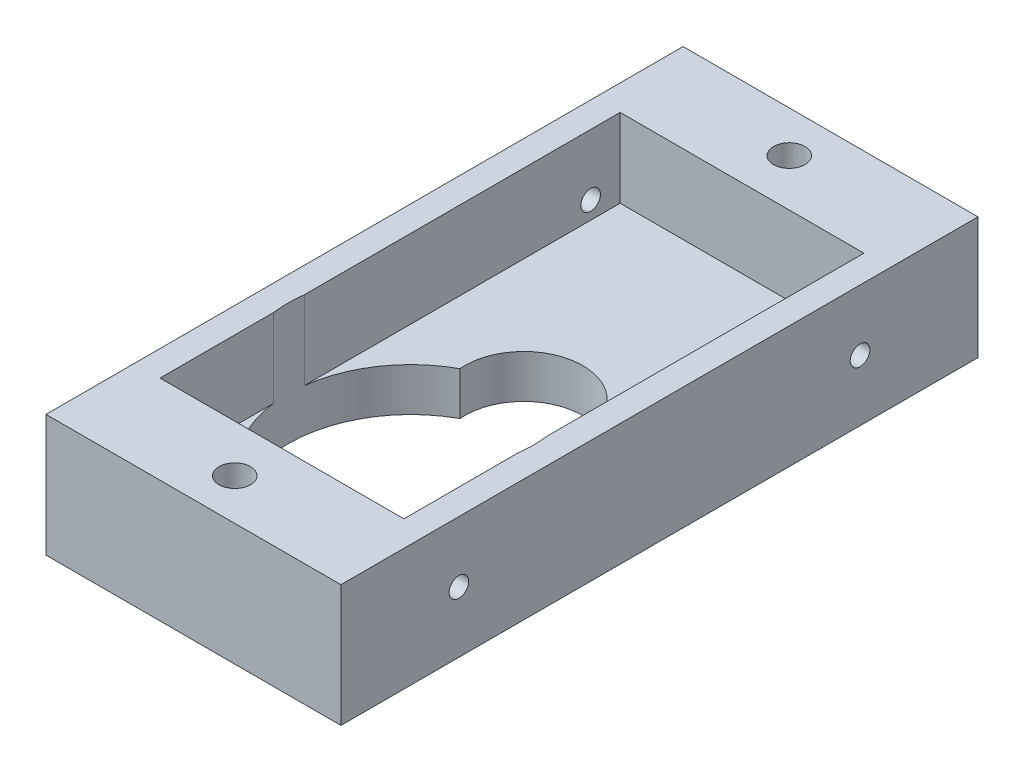
SolidWorks part; units mm, degrees
ref_plane "前视基准面" through (0, 0, 0) normal (0, 0, 1) x (1, 0, 0)
ref_plane "上视基准面" through (0, 0, 0) normal (0, 1, 0) x (1, 0, 0)
ref_plane "右视基准面" through (0, 0, 0) normal (1, 0, 0) x (0, 0, -1)
other "Configuration Table"
sketch "草图1" plane through (0, 0, 0) normal (0, 1, 0) x (1, 0, 0)
  line L1 (0, 0) -> (15, 0)
  line L2 (0, 0) -> (0, -32.4)
  line L3 (0, -32.4) -> (15, -32.4)
  line L4 (15, 0) -> (15, -32.4)
  circle A4 centre (3, -3) radius 0.8
  circle A5 centre (12, -3) radius 0.8
  circle A6 centre (3, -29.4) radius 0.8
  circle A7 centre (12, -29.4) radius 0.8
  circle A8 centre (7.5, -21.35) radius 6.25
  circle A9 centre (7.5, -15.6) radius 3
  point P10 (7.5, -32.4)
  dimension "D3" = 1.6
  dimension "D6" = 12.5
  dimension "D7" = 6
  dimension "D1" = 3
  dimension "D2" = 15
  dimension "D4" = 11.05
  dimension "D5" = 5.75
  dimension "D9" = 3
  dimension "D10" = 3
  dimension "D11" = 3
  dimension "32.4" = 32.4
extrude "凸台-拉伸1" add sketch "草图1" along normal blind 2.2 contours L2 L3 L4 L1 | A7 | A6 | A4 | A5
extrude "切除-拉伸1" cut sketch "草图1<3>" along normal through all contours A9 | A8
sketch "草图1<3>" plane through (0, 0, 0) normal (0, 1, 0) x (1, 0, 0) same geometry as "草图1"
sketch "草图2" plane through (0, 2.2, 0) normal (0, 1, 0) x (1, 0, 0)
  line L0 (0, 0) -> (0, -32.4) construction
  line L1 (15, -32.4) -> (0, -32.4)
  line L2 (15, -32.4) -> (15, -27.9)
  line L3 (15, -27.9) -> (0, -27.9)
  line L4 (0, -32.4) -> (0, -27.9)
  line L6 (15, 0) -> (0, 0)
  line L7 (15, 0) -> (15, -4.5)
  line L8 (15, -4.5) -> (0, -4.5)
  line L9 (0, 0) -> (0, -4.5)
  line L10 (15, -32.4) -> (13.7, -32.4)
  line L11 (15, -32.4) -> (15, 0)
  line L12 (15, 0) -> (13.7, 0)
  line L13 (13.7, -32.4) -> (13.7, 0)
  line L15 (0, 0) -> (1.3, 0)
  line L16 (0, 0) -> (0, -32.4)
  line L17 (0, -32.4) -> (1.3, -32.4)
  line L18 (1.3, 0) -> (1.3, -32.4)
  arc M18 (10.4886, -15.8609) -> (4.5114, -15.8609) centre (7.5, -21.35) cw
  line M19 (15, 0) -> (0, 0)
  line M20 (0, 0) -> (0, -32.4)
  line M21 (0, -32.4) -> (15, -32.4)
  line M22 (15, -32.4) -> (15, 0)
  circle M23 centre (12, -29.4) radius 0.8
  circle M24 centre (3, -29.4) radius 0.8
  circle M25 centre (3, -3) radius 0.8
  circle M26 centre (12, -3) radius 0.8
  dimension "D1" = 4.5
  dimension "D2" = 1.3
  dimension "D3" = 1.3
extrude "凸台-拉伸2" add sketch "草图2" along normal blind 4 contours L6 L18 L8 L13 M25 M26 | L18 L8 M19 M20 | L13 L8 M22 M19 | L3 L18 L1 L13 M24 M23 | L18 L3 M20 M21 | L13 L1 L3 M22 | M25 | M26 | M24 | M23 | L13 L3 L8 M22 M18 | L18 L8 L3 M20 M18 region at (14.35, 2.2, 30.15) region at (7.5, 2.2, 30.2082) region at (14.3511, 2.2, 16.1911) region at (0.65, 2.2, 30.15) region at (14.35, 2.2, 2.25) region at (0.6489, 2.2, 16.1911) region at (7.5, 2.2, 2.1918) region at (0.65, 2.2, 2.25) region at (12, 2.2, 29.4) region at (3, 2.2, 29.4) region at (3, 2.2, 3) region at (12, 2.2, 3)
sketch "草图3" plane through (0, 6.2, 0) normal (0, 1, 0) x (1, 0, 0)
  line L1 (15, 0) -> (0, 0) construction
  line L2 (0, -32.4) -> (15, -32.4) construction
  circle A0 centre (7.5, -30.3) radius 0.8
  circle A1 centre (7.5, -2.1) radius 0.8
  point P11 (7.5, -32.4)
  dimension "D1" = 1.6
  dimension "D2" = 2.1
  dimension "D3" = 2.1
extrude "切除-拉伸2" cut sketch "草图3" against normal blind 3 contours A1 | A0
sketch "草图4" plane through (0, 0, 0) normal (-1, 0, 0) x (0, 0, 1)
  line L0 (0, 6.2) -> (0, 0) construction
  line L1 (6, 3.1) -> (0, 3.1) construction
  line L2 (26.4, 3.1) -> (32.4, 3.1) construction
  line L3 (32.4, 6.2) -> (32.4, 0) construction
  circle A0 centre (6, 3.1) radius 0.5
  circle A1 centre (26.4, 3.1) radius 0.5
  point P6 (0, 3.1)
  point P7 (10.2183, 3.1)
  dimension "D1" = 1
  dimension "D2" = 6
extrude "切除-拉伸3" cut sketch "草图4" against normal through all contours A1 | A0
